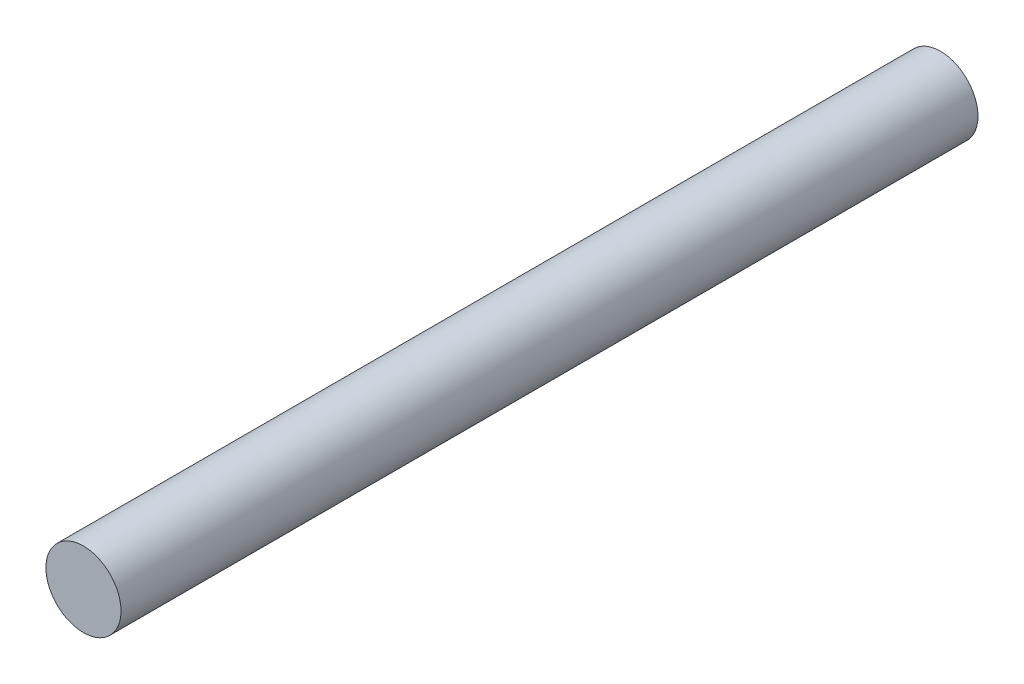
SolidWorks part; units mm, degrees
ref_plane "Front Plane" through (0, 0, 0) normal (0, 0, 1) x (1, 0, 0)
ref_plane "Top Plane" through (0, 0, 0) normal (0, 1, 0) x (1, 0, 0)
ref_plane "Right Plane" through (0, 0, 0) normal (1, 0, 0) x (0, 0, -1)
sketch "Sketch1" plane through (0, 0, 0) normal (0, 0, 1) x (1, 0, 0)
  circle A0 centre (0, 0) radius 5.5626
  dimension "D1" = 11.1252
extrude "Boss-Extrude1" add sketch "Sketch1" along normal blind 127 contours A0
